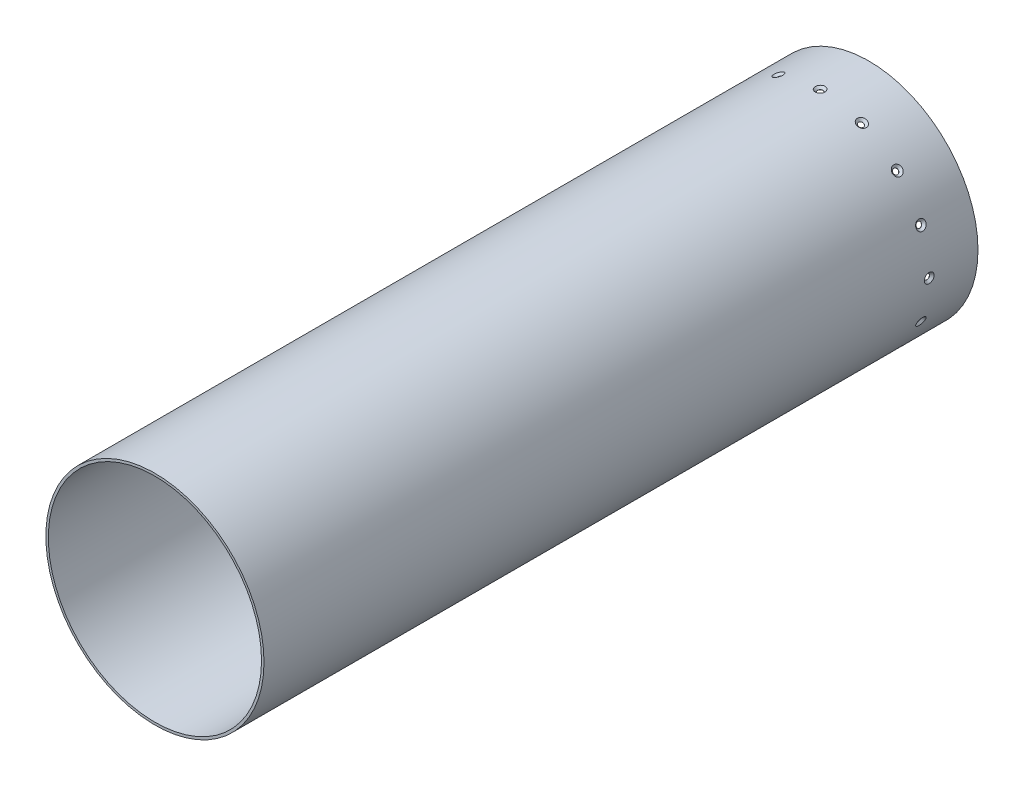
SolidWorks part; units mm, degrees
material "6061-T6 (SS)"
ref_plane "Front Plane" through (0, 0, 0) normal (0, 0, 1) x (1, 0, 0)
ref_plane "Top Plane" through (0, 0, 0) normal (0, 1, 0) x (1, 0, 0)
ref_plane "Right Plane" through (0, 0, 0) normal (1, 0, 0) x (0, 0, -1)
sketch "Sketch1" plane through (0, 0, 0) normal (0, 0, 1) x (1, 0, 0)
  circle A0 centre (0, 0) radius 69.85
  circle A1 centre (0, 0) radius 68.2625
  dimension "D1" = 139.7
  dimension "D2" = 1.5875
extrude "Extrude1" add sketch "Sketch1" along normal blind 457.2
ref_plane "Plane1" through (0, 0, 31.242) normal (0, 0, -1) x (-1, 0, 0)
sketch "Sketch2" plane through (0, 0, 31.242) normal (0, 0, -1) x (-1, 0, 0)
  line L0 (0, 0) -> (0, -69.85) construction
  line L1 (0, 0) -> (-13.6271, -68.5079) construction
  circle A0 centre (0, 0) radius 69.85 construction
  circle A1 centre (0, 0) radius 69.85 construction
  dimension "D1" = 11.25
ref_plane "Plane2" through (0, -69.85, 31.242) normal (0, -1, 0) x (1, 0, 0)
hole_wizard "CSK for M3 Flat Head Machine Screw1" positions "Sketch5" profile "Sketch4" countersink size "M3" standard "Ansi Metric" end condition through all
sketch "Sketch5" plane through (0, -69.85, 31.242) normal (0, -1, 0) x (1, 0, 0)
  point P2 (0, 0)
sketch "Sketch4" plane through (0, -69.85, 31.242) normal (1, 0, 0) x (0, 0, -1)
  line L0 (0, 0) -> (0, 161.1134)
  line L1 (0, 161.1134) -> (1.7, 161.1134)
  line L2 (1.7, 161.1134) -> (1.7, 1.45)
  line L3 (1.7, 1.45) -> (3.15, 0)
  line L5 (3.15, 0) -> (0, 0)
  line L6 (-1.7, 1.45) -> (-3.15, 0) construction
  line L11 (0, -6.35) -> (0, 107.95) construction
  dimension "Thru Hole Dia." = 3.4
  dimension "Thru Hole Depth" = 161.1134
  dimension "Near C'Sink Dia." = 6.3
  dimension "Near C'Sink Angle" = 90
pattern_circular "CirPattern1" count 16 over 360 about axis through (0, 0, 457.2) along (0, 0, -1) of "CSK for M3 Flat Head Machine Screw1"
ref_plane "Plane3" through (0, 0, 446.0875) normal (0, 0, 1) x (1, 0, 0)
ref_plane "Plane5" through (0, 0, 0) normal (0.8315, 0.5556, 0) x (-0.5556, 0.8315, 0)
ref_plane "Plane7" through (0, 0, 0) normal (0.5556, -0.8315, 0) x (0.8315, 0.5556, 0)
ref_plane "Plane9" through (0, 0, 0) normal (-0.1951, -0.9808, 0) x (0.9808, -0.1951, 0)
sketch "Sketch7" plane through (0, 0, 457.2) normal (0, 0, 1) x (1, 0, 0)
  circle A0 centre (0, 0) radius 69.85 construction
  point P0 (69.85, 0)
ref_plane "Plane10" through (13.6271, -68.5079, 31.242) normal (0.1951, -0.9808, 0) x (0.9808, 0.1951, 0)
hole_wizard "#10 Clearance Hole1" positions "Sketch12" profile "Sketch11" hole size "#10" standard "Ansi Inch"
sketch "Sketch12" plane through (13.6271, -68.5079, 31.242) normal (0.1951, -0.9808, 0) x (0.9808, 0.1951, 0)
  point P1 (0, 0)
sketch "Sketch11" plane through (13.6271, -68.5079, 31.242) normal (0, 0, 1) x (0.9808, 0.1951, 0)
  line L0 (0, 0) -> (0, 14.2338)
  line L1 (0, 14.2338) -> (2.5527, 12.7)
  line L2 (2.5527, 12.7) -> (2.5527, 0)
  line L5 (2.5527, 0) -> (0, 0)
  line L10 (0, 14.2338) -> (-2.5527, 12.7) construction
  line L11 (0, -6.35) -> (0, 107.95) construction
  dimension "Hole Dia." = 5.1054
  dimension "Hole Depth" = 12.7
  dimension "Drill Angle" = 118
